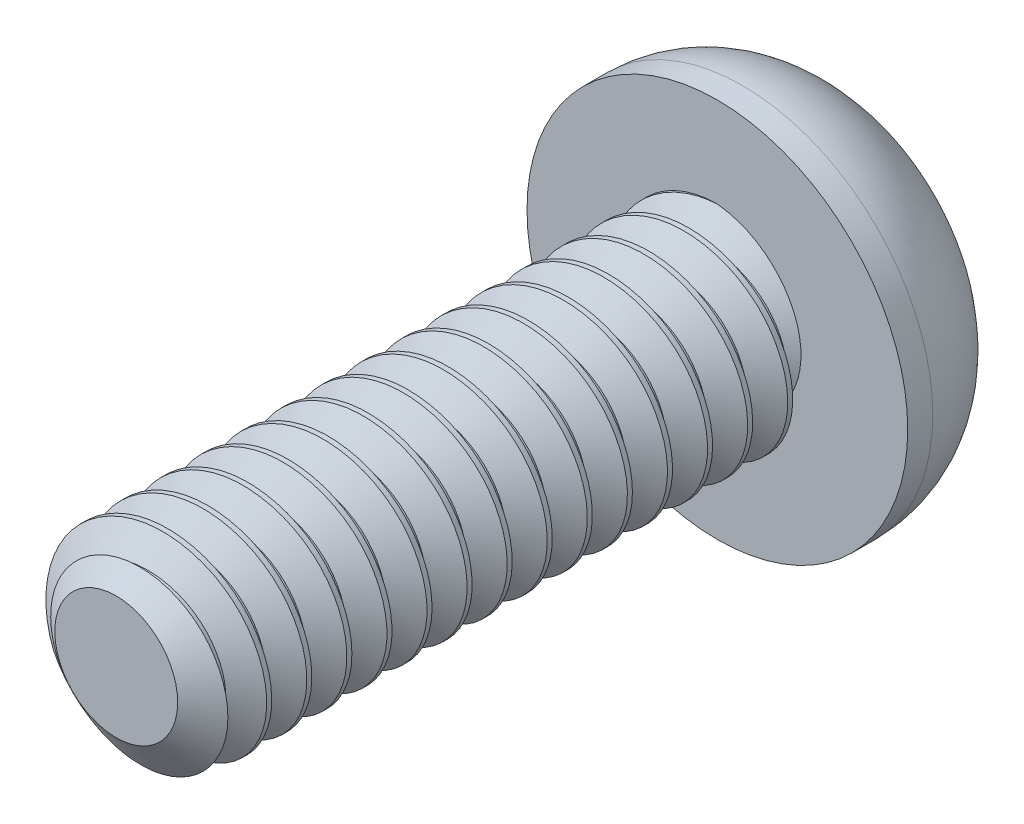
SolidWorks part; units mm, degrees
ref_plane "Front Plane" through (0, 0, 0) normal (0, 0, 1) x (1, 0, 0)
ref_plane "Top Plane" through (0, 0, 0) normal (0, 1, 0) x (1, 0, 0)
ref_plane "Right Plane" through (0, 0, 0) normal (1, 0, 0) x (0, 0, -1)
sketch "Sketch1" plane through (0, 0, 0) normal (0, 0, 1) x (1, 0, 0)
  circle A0 centre (0, 0) radius 2
  dimension "OD" = 4
extrude "Extrude1" add sketch "Sketch1" against normal blind 12
sketch "Sketch2" plane through (0, 0, 0) normal (0, 0, 1) x (1, 0, 0)
  circle A0 centre (0, 0) radius 2 construction
  circle A1 centre (0, 0) radius 2
curve "Helix/Spiral1" pitch 0.8 height 12.8 turns 16 parameters "pitch"=0.8
sketch "Sketch3" plane through (0, 0, 0) normal (1, 0, 0) x (0, 0, -1)
  line L0 (-0.7, 2) -> (-0.4, 1.4804)
  line L1 (-0.4, 1.4804) -> (-0.3, 1.4804)
  line L2 (-0.3, 1.4804) -> (0, 2)
  line L3 (-0.7, 2) -> (0, 2)
  line L4 (-0.35, 2) -> (-0.35, 1.4804) construction
  line L5 (-0.55, 1.7402) -> (-0.15, 1.7402) construction
  line L6 (0, 2) -> (0, -2) construction
  dimension "D1" = 0.1
  dimension "D2" = 0.4
  dimension "D3" = 60
sweep "Cut-Sweep1" cut profiles "Sketch3" path "Helix/Spiral1"
sketch "Sketch4" plane through (0, 0, 0) normal (1, 0, 0) x (0, 0, -1)
  line L0 (0.5417, 2) -> (0, 1.2264)
  line L1 (0, 1.2264) -> (0, 2)
  line L2 (0.5417, 2) -> (0, 2)
  line L3 (-0.7, 2) -> (0, 2) construction
  line L4 (0, 0) -> (7.0209, 0) construction
  dimension "D1" = 55
  dimension "D2" = 0.254
revolve "Cut-Revolve1" cut sketch "Sketch4" angle 360 about L4
sketch "Sketch5" plane through (0, 0, 0) normal (1, 0, 0) x (0, 0, -1)
  line L0 (12, -1.4947) -> (12, 1.4271) construction
  line L1 (12, 2.127) -> (28.1202, 2.127)
  line L2 (12, 2.127) -> (12, 0)
  line L3 (12, 0) -> (28, 0)
  line L4 (28, 1.7968) -> (28, 0)
  line L5 (28.1202, 2.127) -> (28, 1.7968)
  line L6 (0, 0) -> (9.9695, 0) construction
  point P3 (28, 2.127)
  point P10 (28, 2.127)
  dimension "D1" = 0.3302
  dimension "Thread min" = 28
  dimension "D2" = 0.127
  dimension "D3" = 20
sketch "Sketch6" plane through (0, 0, -12) normal (0, 0, -1) x (-1, 0, 0)
  circle A0 centre (0, 0) radius 3.8
  dimension "head dia" = 7.6
extrude "Extrude2" add sketch "Sketch6" along normal blind 2.75
sketch "Sketch10" plane through (0, 0, 0) normal (1, 0, 0) x (0, 0, -1)
  line L0 (14.75, -3.8) -> (14.75, 3.8) construction
  line L1 (0, 0) -> (15.9584, 0) construction
  line L2 (14.75, 3.8) -> (12, 3.8) construction
  line L3 (12, 3.8) -> (12, -3.8) construction
  line L4 (12.5, 3.8) -> (12.5, 4.3)
  line L5 (12.5, 4.3) -> (15.25, 4.3)
  line L6 (15.25, 4.3) -> (15.25, 1.5)
  line L7 (14.75, 1.5) -> (15.25, 1.5)
  arc A0 (14.75, 1.5) -> (12.5, 3.8) centre (12.4494, 1.5) ccw
  dimension "D1" = 3
  dimension "D2" = 0.5
  dimension "D3" = 0.5
revolve "Cut-Revolve2" cut sketch "Sketch10" angle 360 about L1
ref_plane "Plane1" through (0, 0, -14.75) normal (0, 0, 1) x (1, 0, 0)
sketch "Sketch7" plane through (0, 0, -14.75) normal (0, 0, -1) x (-1, 0, 0)
  line L1 (0, 1.7321) -> (-1.5, 0.866)
  line L2 (-1.5, 0.866) -> (-1.5, -0.866)
  line L3 (-1.5, -0.866) -> (0, -1.7321)
  line L4 (0, -1.7321) -> (1.5, -0.866)
  line L5 (1.5, -0.866) -> (1.5, 0.866)
  line L6 (1.5, 0.866) -> (0, 1.7321)
  circle A0 centre (0, 0) radius 1.5 construction
  dimension "hex dia" = 3
extrude "Cut-Extrude1" cut sketch "Sketch7" against normal blind 2.25
sketch "Sketch8" plane through (0, 0, -14.75) normal (0, 0, 1) x (1, 0, 0)
  circle A0 centre (0, 0) radius 1.7321
extrude "Cut-Extrude2" cut sketch "Sketch8" along normal through all draft 45
sketch "Sketch9" plane through (0, 0, 0) normal (1, 0, 0) x (0, 0, -1)
  line L0 (0, 2) -> (0, -2) construction
  line L1 (4.4, 2) -> (4.4, -2) construction
  dimension "D1" = 4.4
equation "\"D3@Helix/Spiral1\" = \"screw length@Extrude1\"+\"pitch@Helix/Spiral1\""
equation "\"D1@Sketch3\" = \"pitch@Helix/Spiral1\"*.125"
equation "\"D2@Sketch3\" = \"pitch@Helix/Spiral1\"*.5"
equation "\"D1@Cut-Extrude1\" = \"hex dia@Sketch7\"*.75"
equation "\"D1@Sketch9\" = \"pitch@Helix/Spiral1\"*5.5"
equation "\"D1@Sketch10\" = \"hex dia@Sketch7\""
equation "\"D1@Plane1\" = \"head depth@Extrude2\""
